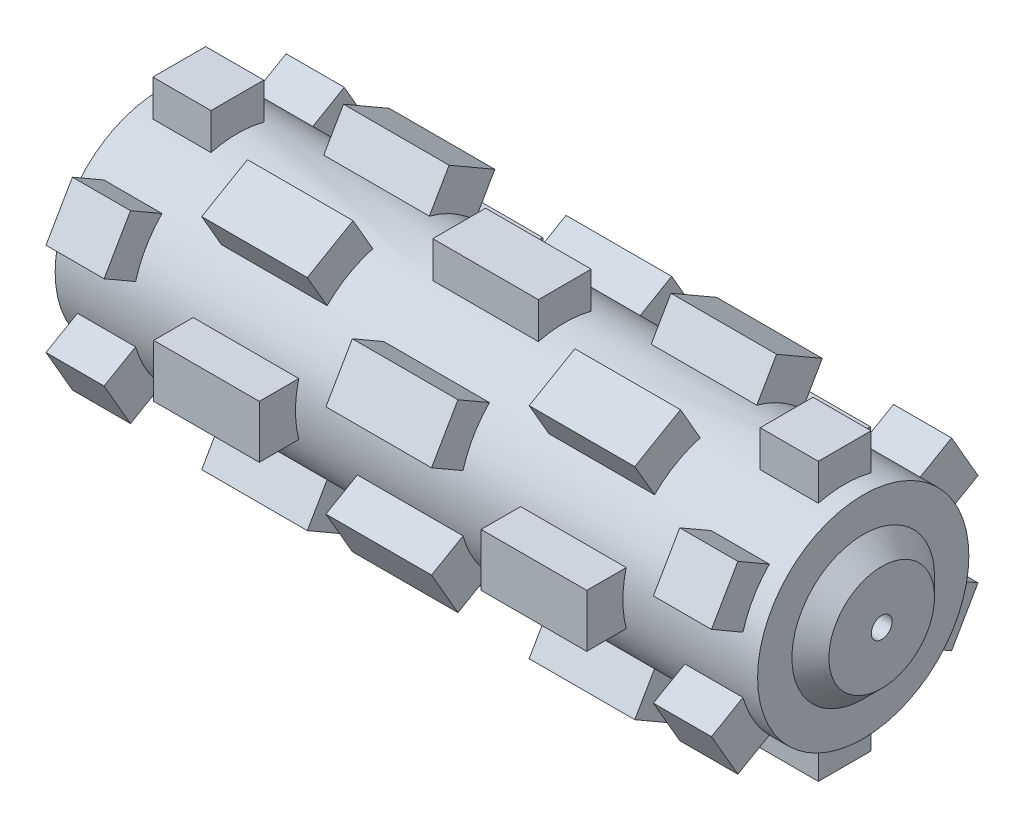
SolidWorks part; units mm, degrees
ref_plane "Front Plane" through (0, 0, 0) normal (0, 0, 1) x (1, 0, 0)
ref_plane "Top Plane" through (0, 0, 0) normal (0, 1, 0) x (1, 0, 0)
ref_plane "Right Plane" through (0, 0, 0) normal (1, 0, 0) x (0, 0, -1)
sketch "Sketch1" plane through (0, 0, 0) normal (1, 0, 0) x (0, 0, -1)
  line L0 (0, -34.925) -> (0, 34.925) construction
  line L1 (-12.7, 66.675) -> (12.7, 66.675)
  line L2 (-12.7, 66.675) -> (-12.7, 34.925)
  line L3 (-12.7, 34.925) -> (12.7, 34.925)
  line L4 (12.7, 66.675) -> (12.7, 34.925)
  line L5 (-12.7, 66.675) -> (12.7, 34.925) construction
  line L6 (-12.7, 34.925) -> (12.7, 66.675) construction
  line L7 (51.3922, 44.336) -> (23.8959, 28.461)
  line L8 (51.3922, 44.336) -> (64.0922, 22.339)
  line L9 (64.0922, 22.339) -> (36.5959, 6.464)
  line L10 (23.8959, 28.461) -> (36.5959, 6.464)
  line L11 (64.0922, -22.339) -> (36.5959, -6.464)
  line L12 (64.0922, -22.339) -> (51.3922, -44.336)
  line L13 (51.3922, -44.336) -> (23.8959, -28.461)
  line L14 (36.5959, -6.464) -> (23.8959, -28.461)
  line L15 (12.7, -66.675) -> (12.7, -34.925)
  line L16 (12.7, -66.675) -> (-12.7, -66.675)
  line L17 (-12.7, -66.675) -> (-12.7, -34.925)
  line L18 (12.7, -34.925) -> (-12.7, -34.925)
  line L19 (-51.3922, -44.336) -> (-23.8959, -28.461)
  line L20 (-51.3922, -44.336) -> (-64.0922, -22.339)
  line L21 (-64.0922, -22.339) -> (-36.5959, -6.464)
  line L22 (-23.8959, -28.461) -> (-36.5959, -6.464)
  line L23 (-64.0922, 22.339) -> (-36.5959, 6.464)
  line L24 (-64.0922, 22.339) -> (-51.3922, 44.336)
  line L25 (-51.3922, 44.336) -> (-23.8959, 28.461)
  line L26 (-36.5959, 6.464) -> (-23.8959, 28.461)
  circle A0 centre (0, 0) radius 50.8
  point P3 (0, 50.8)
  point P10 (0, 0)
  point P12 (0, 0)
  point P14 (0, 0)
  point P34 (0, 0)
  dimension "D1" = 101.6
  dimension "D3" = 25.4
  dimension "D4" = 31.75
  dimension "D2" = 6
extrude "Boss-Extrude3" add sketch "Sketch1" along normal blind 50.8 contours A0 | L2 L1 L4 L3 | L23 L26 L25 L24 | L19 L22 L21 L20 | L15 L18 L17 L16 | L11 L14 L13 L12 | L7 L10 L9 L8
sketch "Sketch2" plane through (50.8, 0, 0) normal (1, 0, 0) x (0, 0, -1)
  circle A0 centre (0, 0) radius 50.8
extrude "Boss-Extrude4" add sketch "Sketch2" along normal blind 27.94
sketch "Sketch3" plane through (78.74, 0, 0) normal (1, 0, 0) x (0, 0, -1)
  line L0 (0, 0) -> (12.7, 66.675) construction
  line L1 (12.7, 66.675) -> (12.7, 49.1869) construction
  line L2 (36.4373, 12.7) -> (36.4373, 0)
  line L3 (51.3922, 44.336) -> (0, 0) construction
  line L4 (34.0936, 59.0519) -> (0, 0) construction
  line L5 (18.2186, 31.5556) -> (29.2172, 25.2056)
  line L6 (29.2172, 25.2056) -> (45.0922, 52.7019)
  line L7 (45.0922, 52.7019) -> (23.0951, 65.4019)
  line L8 (23.0951, 65.4019) -> (7.2201, 37.9056)
  line L9 (7.2201, 37.9056) -> (18.2186, 31.5556)
  line L10 (36.4373, 0) -> (36.4373, -12.7)
  line L11 (36.4373, -12.7) -> (68.1873, -12.7)
  line L12 (68.1873, -12.7) -> (68.1873, 12.7)
  line L13 (68.1873, 12.7) -> (36.4373, 12.7)
  line L14 (29.2172, -25.2056) -> (18.2186, -31.5556)
  line L15 (18.2186, -31.5556) -> (7.2201, -37.9056)
  line L16 (7.2201, -37.9056) -> (23.0951, -65.4019)
  line L17 (23.0951, -65.4019) -> (45.0922, -52.7019)
  line L18 (45.0922, -52.7019) -> (29.2172, -25.2056)
  line L19 (-7.2201, -37.9056) -> (-18.2186, -31.5556)
  line L20 (-18.2186, -31.5556) -> (-29.2172, -25.2056)
  line L21 (-29.2172, -25.2056) -> (-45.0922, -52.7019)
  line L22 (-45.0922, -52.7019) -> (-23.0951, -65.4019)
  line L23 (-23.0951, -65.4019) -> (-7.2201, -37.9056)
  line L24 (-36.4373, -12.7) -> (-36.4373, 0)
  line L25 (-36.4373, 0) -> (-36.4373, 12.7)
  line L26 (-36.4373, 12.7) -> (-68.1873, 12.7)
  line L27 (-68.1873, 12.7) -> (-68.1873, -12.7)
  line L28 (-68.1873, -12.7) -> (-36.4373, -12.7)
  line L29 (-29.2172, 25.2056) -> (-18.2186, 31.5556)
  line L30 (-18.2186, 31.5556) -> (-7.2201, 37.9056)
  line L31 (-7.2201, 37.9056) -> (-23.0951, 65.4019)
  line L32 (-23.0951, 65.4019) -> (-45.0922, 52.7019)
  line L33 (-45.0922, 52.7019) -> (-29.2172, 25.2056)
  circle A0 centre (0, 0) radius 50.8
  circle A1 centre (0, 0) radius 67.8737 construction
  point P44 (0, 0)
  dimension "D1" = 31.75
  dimension "D2" = 25.4
  dimension "D3" = 6
extrude "Boss-Extrude5" add sketch "Sketch3" along normal blind 50.8 contours A0 | L24 L25 L26 L27 L28 | L29 L30 L31 L32 L33 | L9 L5 L6 L7 L8 | L2 L10 L11 L12 L13 | L14 L15 L16 L17 L18 | L19 L20 L21 L22 L23
sketch "Sketch4" plane through (129.54, 0, 0) normal (1, 0, 0) x (0, 0, -1)
  circle A0 centre (0, 0) radius 50.8
extrude "Boss-Extrude6" add sketch "Sketch4" along normal blind 27.94
sketch "Sketch5" plane through (157.48, 0, 0) normal (1, 0, 0) x (0, 0, -1)
  line L0 (12.7, 66.675) -> (12.7, 49.1869) construction
  line L1 (-12.7, 66.675) -> (12.7, 66.675)
  line L2 (-12.7, 66.675) -> (-12.7, 34.925)
  line L3 (-12.7, 34.925) -> (12.7, 34.925)
  line L4 (12.7, 66.675) -> (12.7, 34.925)
  line L5 (51.3922, 44.336) -> (23.8959, 28.461)
  line L6 (51.3922, 44.336) -> (64.0922, 22.339)
  line L7 (64.0922, 22.339) -> (36.5959, 6.464)
  line L8 (23.8959, 28.461) -> (36.5959, 6.464)
  line L9 (64.0922, -22.339) -> (36.5959, -6.464)
  line L10 (64.0922, -22.339) -> (51.3922, -44.336)
  line L11 (51.3922, -44.336) -> (23.8959, -28.461)
  line L12 (36.5959, -6.464) -> (23.8959, -28.461)
  line L13 (12.7, -66.675) -> (12.7, -34.925)
  line L14 (12.7, -66.675) -> (-12.7, -66.675)
  line L15 (-12.7, -66.675) -> (-12.7, -34.925)
  line L16 (12.7, -34.925) -> (-12.7, -34.925)
  line L17 (-51.3922, -44.336) -> (-23.8959, -28.461)
  line L18 (-51.3922, -44.336) -> (-64.0922, -22.339)
  line L19 (-64.0922, -22.339) -> (-36.5959, -6.464)
  line L20 (-23.8959, -28.461) -> (-36.5959, -6.464)
  line L21 (-64.0922, 22.339) -> (-36.5959, 6.464)
  line L22 (-64.0922, 22.339) -> (-51.3922, 44.336)
  line L23 (-51.3922, 44.336) -> (-23.8959, 28.461)
  line L24 (-36.5959, 6.464) -> (-23.8959, 28.461)
  circle A0 centre (0, 0) radius 50.8
  point P33 (0, 0)
  dimension "D1" = 31.75
  dimension "D2" = 25.4
  dimension "D3" = 6
extrude "Boss-Extrude7" add sketch "Sketch5" along normal blind 27.94 contours A0 | L21 L24 L23 L22 | L2 L1 L4 L3 | L5 L8 L7 L6 | L17 L20 L19 L18 | L13 L16 L15 L14 | L9 L12 L11 L10
sketch "Sketch6" plane through (0, 0, 0) normal (-1, 0, 0) x (0, 0, 1)
  circle A0 centre (0, 0) radius 50.8
extrude "Boss-Extrude8" add sketch "Sketch6" along normal blind 27.94
sketch "Sketch7" plane through (-27.94, 0, 0) normal (-1, 0, 0) x (0, 0, 1)
  line L0 (23.0951, 65.4019) -> (45.0922, 52.7019)
  line L1 (45.0922, 52.7019) -> (29.2172, 25.2056)
  line L2 (29.2172, 25.2056) -> (7.2201, 37.9056)
  line L3 (7.2201, 37.9056) -> (23.0951, 65.4019)
  line L4 (36.4373, 12.7) -> (68.1873, 12.7)
  line L5 (68.1873, 12.7) -> (68.1873, -12.7)
  line L6 (68.1873, -12.7) -> (36.4373, -12.7)
  line L7 (36.4373, -12.7) -> (36.4373, 12.7)
  line L8 (29.2172, -25.2056) -> (45.0922, -52.7019)
  line L9 (45.0922, -52.7019) -> (23.0951, -65.4019)
  line L10 (23.0951, -65.4019) -> (7.2201, -37.9056)
  line L11 (7.2201, -37.9056) -> (29.2172, -25.2056)
  line L12 (-7.2201, -37.9056) -> (-23.0951, -65.4019)
  line L13 (-23.0951, -65.4019) -> (-45.0922, -52.7019)
  line L14 (-45.0922, -52.7019) -> (-29.2172, -25.2056)
  line L15 (-29.2172, -25.2056) -> (-7.2201, -37.9056)
  line L16 (-36.4373, -12.7) -> (-68.1873, -12.7)
  line L17 (-68.1873, -12.7) -> (-68.1873, 12.7)
  line L18 (-68.1873, 12.7) -> (-36.4373, 12.7)
  line L19 (-36.4373, 12.7) -> (-36.4373, -12.7)
  line L20 (-29.2172, 25.2056) -> (-45.0922, 52.7019)
  line L21 (-45.0922, 52.7019) -> (-23.0951, 65.4019)
  line L22 (-23.0951, 65.4019) -> (-7.2201, 37.9056)
  line L23 (-7.2201, 37.9056) -> (-29.2172, 25.2056)
  circle A0 centre (0, 0) radius 50.8
  point P28 (0, 0)
  dimension "D1" = 25.4
  dimension "D2" = 31.75
  dimension "D3" = 6
extrude "Boss-Extrude9" add sketch "Sketch7" along normal blind 50.8 contours L3 L0 L1 L2 | L20 L21 L22 L23 | A0 | L16 L17 L18 L19 | L12 L13 L14 L15 | L8 L9 L10 L11 | L4 L5 L6 L7
sketch "Sketch8" plane through (-78.74, 0, 0) normal (-1, 0, 0) x (0, 0, 1)
  circle A0 centre (0, 0) radius 50.8
extrude "Boss-Extrude10" add sketch "Sketch8" along normal blind 27.94
sketch "Sketch9" plane through (-106.68, 0, 0) normal (-1, 0, 0) x (0, 0, 1)
  line L0 (12.7, 66.675) -> (12.7, 49.1869) construction
  line L1 (-12.7, 66.675) -> (12.7, 66.675)
  line L2 (-12.7, 66.675) -> (-12.7, 34.925)
  line L3 (-12.7, 34.925) -> (12.7, 34.925)
  line L4 (12.7, 66.675) -> (12.7, 34.925)
  line L5 (51.3922, 44.336) -> (23.8959, 28.461)
  line L6 (51.3922, 44.336) -> (64.0922, 22.339)
  line L7 (64.0922, 22.339) -> (36.5959, 6.464)
  line L8 (23.8959, 28.461) -> (36.5959, 6.464)
  line L9 (64.0922, -22.339) -> (36.5959, -6.464)
  line L10 (64.0922, -22.339) -> (51.3922, -44.336)
  line L11 (51.3922, -44.336) -> (23.8959, -28.461)
  line L12 (36.5959, -6.464) -> (23.8959, -28.461)
  line L13 (12.7, -66.675) -> (12.7, -34.925)
  line L14 (12.7, -66.675) -> (-12.7, -66.675)
  line L15 (-12.7, -66.675) -> (-12.7, -34.925)
  line L16 (12.7, -34.925) -> (-12.7, -34.925)
  line L17 (-51.3922, -44.336) -> (-23.8959, -28.461)
  line L18 (-51.3922, -44.336) -> (-64.0922, -22.339)
  line L19 (-64.0922, -22.339) -> (-36.5959, -6.464)
  line L20 (-23.8959, -28.461) -> (-36.5959, -6.464)
  line L21 (-64.0922, 22.339) -> (-36.5959, 6.464)
  line L22 (-64.0922, 22.339) -> (-51.3922, 44.336)
  line L23 (-51.3922, 44.336) -> (-23.8959, 28.461)
  line L24 (-36.5959, 6.464) -> (-23.8959, 28.461)
  circle A0 centre (0, 0) radius 50.8
  point P33 (0, 0)
  dimension "D1" = 31.75
  dimension "D2" = 25.4
  dimension "D3" = 6
extrude "Boss-Extrude11" add sketch "Sketch9" along normal blind 27.94 contours A0 | L21 L24 L23 L22 | L17 L20 L19 L18 | L13 L16 L15 L14 | L9 L12 L11 L10 | L5 L8 L7 L6 | L2 L1 L4 L3
sketch "Sketch10" plane through (185.42, 0, 0) normal (1, 0, 0) x (0, 0, -1)
  circle A0 centre (0, 0) radius 50.8
extrude "Boss-Extrude12" add sketch "Sketch10" along normal blind 8.89
sketch "Sketch11" plane through (-134.62, 0, 0) normal (-1, 0, 0) x (0, 0, 1)
  circle A0 centre (0, 0) radius 50.8
extrude "Boss-Extrude13" add sketch "Sketch11" along normal blind 8.89
sketch "Sketch12" plane through (194.31, 0, 0) normal (1, 0, 0) x (0, 0, -1)
  circle A1 centre (0, 0) radius 25.4
  dimension "D2" = 50.8
extrude "Boss-Extrude14" add sketch "Sketch12" along normal blind 8.89
sketch "Sketch13" plane through (-143.51, 0, 0) normal (-1, 0, 0) x (0, 0, 1)
  circle A0 centre (0, 0) radius 25.4
  dimension "D1" = 50.8
extrude "Boss-Extrude15" add sketch "Sketch13" along normal blind 8.89
sketch "Sketch14" plane through (-152.4, 0, 0) normal (-1, 0, 0) x (0, 0, 1)
  circle A0 centre (0, 0) radius 5
  dimension "D1" = 10
extrude "Cut-Extrude1" cut sketch "Sketch14" against normal through all
chamfer "Chamfer3" distance 8.89 angle 45 2 edges at (-143.51, 0, 25.4) (194.31, 0, -25.4)
